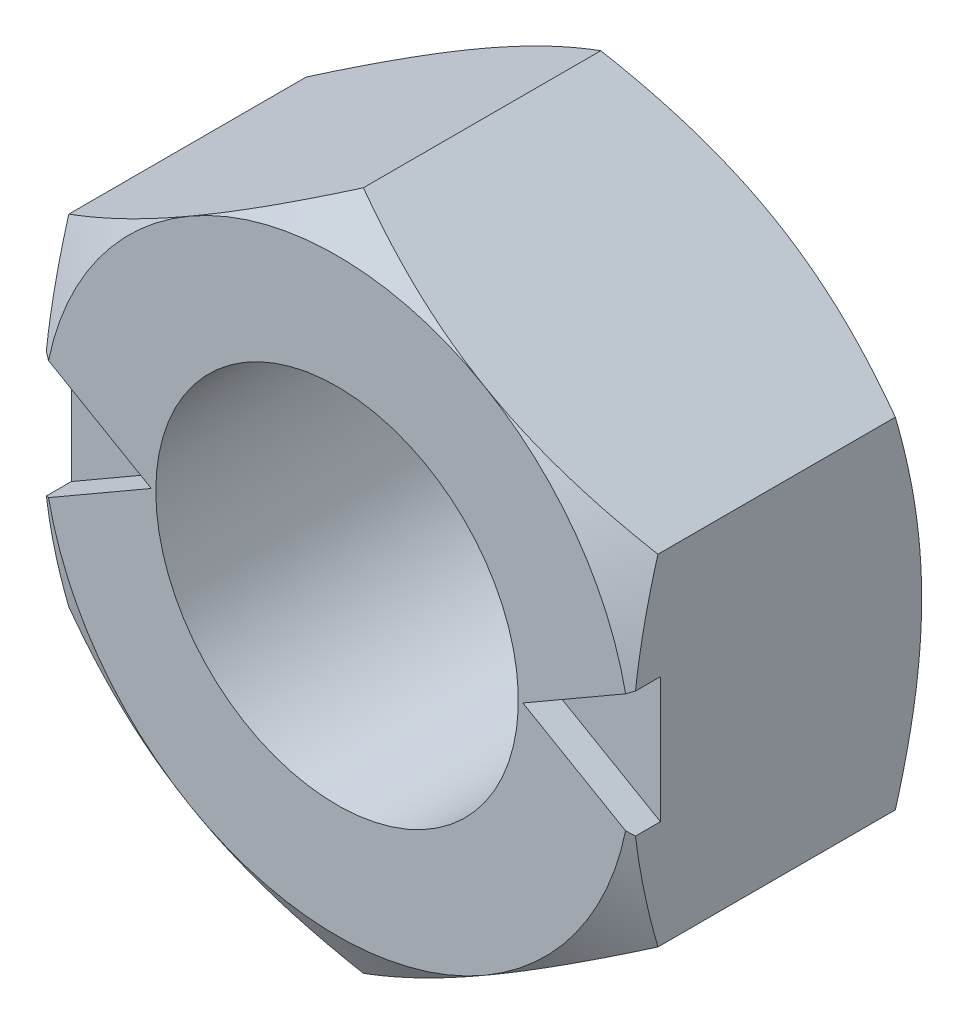
SolidWorks part; units mm, degrees
ref_plane "Front Plane" through (0, 0, 0) normal (0, 0, 1) x (1, 0, 0)
ref_plane "Top Plane" through (0, 0, 0) normal (0, 1, 0) x (1, 0, 0)
ref_plane "Right Plane" through (0, 0, 0) normal (1, 0, 0) x (0, 0, -1)
sketch "Sketch10" plane through (0, 0, 0) normal (1, 0, 0) x (0, 0, -1)
  line L0 (-3.2, 0) -> (3.2, 0) construction
  line L1 (-3.2, -6.5) -> (-3.2, 6.5) construction
  line L2 (-3.2, -4) -> (-3.2, 4) construction
  line L3 (-4.3719, 4.1353) -> (-3.1219, 4.1353) construction
  line L4 (-3.1219, 4.1353) -> (-3.7469, 3.0528) construction
  line L5 (-3.7469, 3.0528) -> (-4.3719, 4.1353) construction
  line L6 (-3.7469, 4.1353) -> (-3.7469, 4) construction
  line L7 (-3.7469, 3.0528) -> (-3.7469, 3.1881) construction
  line L8 (-4.2937, 4) -> (-3.2, 4) construction
  line L9 (-4.3328, 4.0677) -> (-3.1609, 4.0677) construction
  line L10 (-3.825, 3.1881) -> (-3.6687, 3.1881) construction
  line L11 (3.2, -6.5) -> (3.2, 6.5) construction
  point P4 (0, 0)
  point P8 (-3.2, 0)
  point P11 (-3.2, 0)
  point P20 (-3.7469, 4)
  point P23 (-3.7469, 4.0677)
  point P26 (-3.7469, 3.1881)
  point P27 (-2.565, 0)
  point P28 (3.2, 0)
  dimension "Height" = 6.4
  dimension "Width" = 13
  dimension "Thread Size" = 8
  dimension "Thread Pitch" = 1.25
  dimension "D1" = 0.1562
  dimension "D2" = 0.635
sketch "Sketch11" plane through (0, 0, 0) normal (0, 0, 1) x (1, 0, 0)
  line L0 (0, -6.5) -> (0, 6.5) construction
  line L1 (-6.5, 0) -> (-4.1, 0) construction
  line L2 (-4.1, 0) -> (-6.5, 1.3856) construction
  line L3 (-6.5, 1.3856) -> (-6.5, 0) construction
  line L4 (0, 0) -> (2.8284, -2.8284) construction
  circle A0 centre (0, 0) radius 4 construction
  circle A1 centre (0, 0) radius 6.5 construction
  point P10 (-4, 0)
  point P14 (2.8284, -2.8284)
  dimension "D1" = 0.1
  dimension "D2" = 30
  dimension "D3" = 135
sketch "Sketch1" plane through (0, 0, 0) normal (0, 0, 1) x (1, 0, 0)
  line L1 (0, 7.5056) -> (-6.5, 3.7528)
  line L2 (-6.5, 3.7528) -> (-6.5, -3.7528)
  line L3 (-6.5, -3.7528) -> (0, -7.5056)
  line L4 (0, -7.5056) -> (6.5, -3.7528)
  line L5 (6.5, -3.7528) -> (6.5, 3.7528)
  line L6 (6.5, 3.7528) -> (0, 7.5056)
  circle A0 centre (0, 0) radius 6.5 construction
  circle A1 centre (0, 0) radius 6.5 construction
extrude "Extrude1" add sketch "Sketch1" along normal up to vertex (3.2 mm away) and the other way up to vertex (3.2 mm away) up to point (0, 0, 3.2) other way up to point (0, 0, -3.2)
sketch "Sketch2" plane through (0, 0, 3.2) normal (0, 0, -1) x (-1, 0, 0)
  circle A1 centre (0, 0) radius 6.5
  circle A2 centre (0, 0) radius 6.5 construction
extrude "Cut-Extrude1" cut sketch "Sketch2" along normal through all draft 60 flip side to cut
sketch "Sketch3" plane through (0, 0, -3.2) normal (0, 0, 1) x (1, 0, 0)
  circle A0 centre (0, 0) radius 6.5 construction
  circle A2 centre (0, 0) radius 6.5
extrude "Cut-Extrude2" cut sketch "Sketch3" along normal through all draft 60 flip side to cut
sketch "Sketch4" plane through (0, 0, -3.2) normal (0, 0, -1) x (-1, 0, 0)
  circle A0 centre (0, 0) radius 4
  circle A1 centre (0, 0) radius 4 construction
extrude "Cut-Extrude3" cut sketch "Sketch4" against normal through all
sketch "Sketch12" plane through (0, 0, 3.2) normal (0, 0, 1) x (1, 0, 0)
  line L0 (-4.1, 0) -> (-6.5, 1.3856) construction
  line L1 (-4.1, 0) -> (-6.5, 1.3856)
  line L2 (-6.5, 0) -> (-4.1, 0) construction
  line L3 (-6.5, 0) -> (-4.1, 0) construction
  line L4 (0, -4) -> (0, 4) construction
  line L5 (0, -4) -> (0, 4) construction
  line L6 (-4.1, 0) -> (-6.5, -1.3856)
  line L7 (4.1, 0) -> (6.5, -1.3856)
  line L8 (4.1, 0) -> (6.5, 1.3856)
  line L9 (-6.5, 1.3856) -> (-6.5, -1.3856)
  line L10 (6.5, 1.3856) -> (6.5, -1.3856)
extrude "Cut-Extrude7" cut sketch "Sketch12" against normal up to vertex (0.635 mm away) up to point (0, 0, 2.565)
sketch "Sketch5" [suppressed] plane through (0, 0, 3.2) normal (0, 0, -1) x (-1, 0, 0)
  circle A1 centre (0, 0) radius 4
  point P0 (0, 4)
curve "Helix/Spiral1" [suppressed] pitch 1.25 height 7.65 turns 6.12 parameters "pitch"=1.25
sketch "Sketch6" [suppressed] plane through (0, 0, 0) normal (1, 0, 0) x (0, 0, -1)
  line L0 (-4.3328, 4.0677) -> (-3.1609, 4.0677)
  line L1 (-3.1609, 4.0677) -> (-3.6687, 3.1881)
  line L2 (-3.6687, 3.1881) -> (-3.825, 3.1881)
  line L3 (-3.825, 3.1881) -> (-4.3328, 4.0677)
sweep "Sweep1" [suppressed] add profiles "Sketch6" path "Helix/Spiral1"
sketch "Sketch7" [suppressed] plane through (0, 0, -3.2) normal (0, 0, -1) x (-1, 0, 0)
  circle A0 centre (0, 0) radius 4.1353
  point P2 (0, 4.1353)
extrude "Cut-Extrude4" [suppressed] cut sketch "Sketch7" against normal through all draft 45 and the other way through all
sketch "Sketch8" [suppressed] plane through (0, 0, 3.2) normal (0, 0, 1) x (1, 0, 0)
  line L0 (0, 0) -> (-3.5813, 2.0677) construction
  circle A1 centre (0, 0) radius 4.1353
  circle A2 centre (0, 0) radius 4.1353
  dimension "D1" = 0
extrude "Cut-Extrude5" [suppressed] cut sketch "Sketch8" against normal through all draft 45 and the other way through all
equation "\"D3@Helix/Spiral1\" = \"Thread Pitch@Sketch10\" + \"Height@Sketch10\""
equation "\"D1@Sketch10\" = \"Thread Pitch@Sketch10\" / 8"
equation "\"pitch@Helix/Spiral1\" = \"Thread Pitch@Sketch10\""
